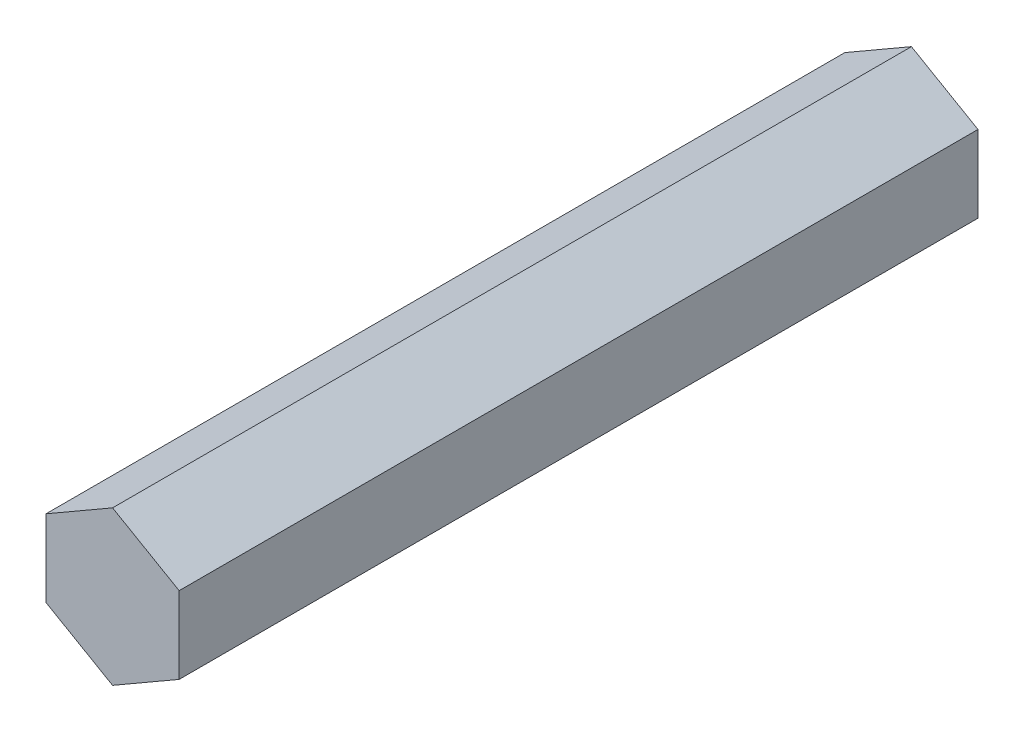
SolidWorks part; units mm, degrees
ref_plane "Piano frontale" through (0, 0, 0) normal (0, 0, 1) x (1, 0, 0)
ref_plane "Piano superiore" through (0, 0, 0) normal (0, 1, 0) x (1, 0, 0)
ref_plane "Piano destro" through (0, 0, 0) normal (1, 0, 0) x (0, 0, -1)
sketch "Schizzo1" plane through (0, 0, 0) normal (0, 0, 1) x (1, 0, 0)
  line L1 (0, -16.9648) -> (-2.5, -18.4081)
  line L2 (-2.5, -18.4081) -> (-2.5, -21.2949)
  line L3 (-2.5, -21.2949) -> (0, -22.7383)
  line L4 (0, -22.7383) -> (2.5, -21.2949)
  line L5 (2.5, -21.2949) -> (2.5, -18.4081)
  line L6 (2.5, -18.4081) -> (0, -16.9648)
  circle A0 centre (0, -19.8515) radius 2.5 construction
  dimension "D1" = 5
extrude "Estrusione-Estrusione1" add sketch "Schizzo1" along normal blind 30
